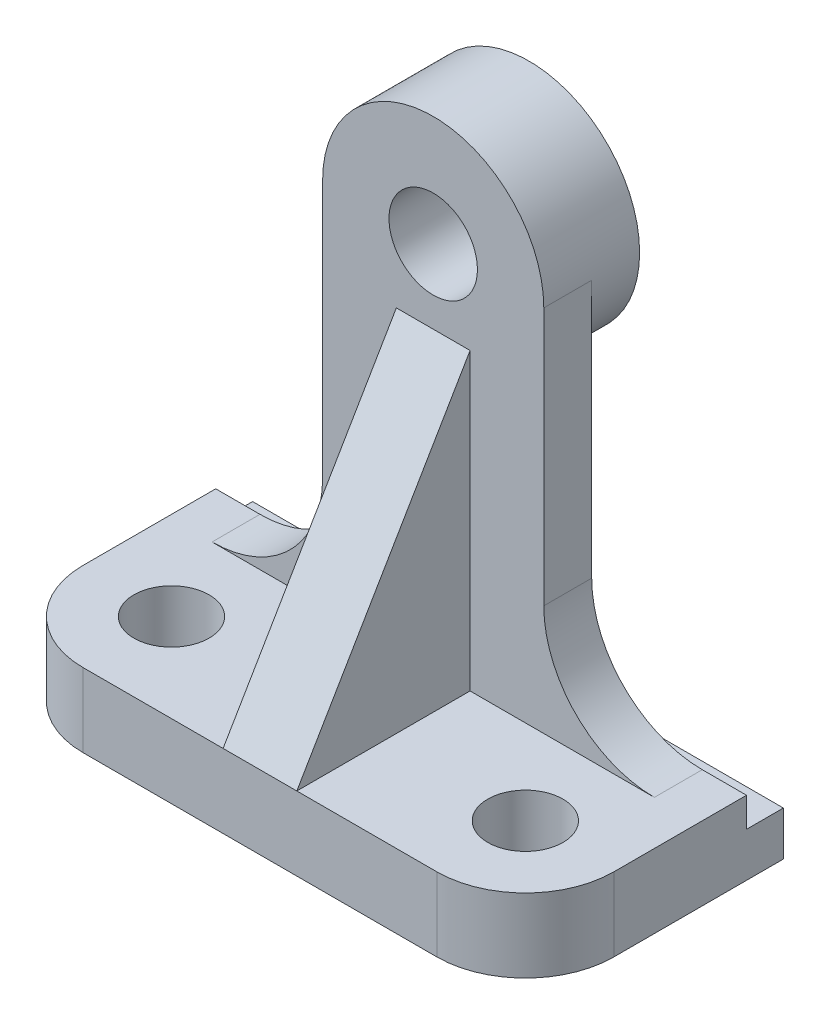
SolidWorks part; units mm, degrees
ref_plane "Front Plane" through (0, 0, 0) normal (0, 0, 1) x (1, 0, 0)
ref_plane "Top Plane" through (0, 0, 0) normal (0, 1, 0) x (1, 0, 0)
ref_plane "Right Plane" through (0, 0, 0) normal (1, 0, 0) x (0, 0, -1)
sketch "Sketch1" plane through (0, 0, 0) normal (0, 1, 0) x (1, 0, 0)
  line L0 (0, 22.4528) -> (0, -21.3843) construction
  line L1 (-36, -17.5) -> (36, -17.5)
  line L2 (-36, -17.5) -> (-36, 17.5)
  line L3 (-36, 17.5) -> (36, 17.5)
  line L4 (36, -17.5) -> (36, 17.5)
  line L5 (-36, -17.5) -> (36, 17.5) construction
  line L6 (-36, 17.5) -> (36, -17.5) construction
  circle A0 centre (24, -5.5) radius 5.1
  circle A1 centre (-24, -5.5) radius 5.1
  point P0 (0, 0)
  dimension "D4" = 10.2
  dimension "D1" = 35
  dimension "D2" = 72
  dimension "D3" = 24
  dimension "D5" = 12
extrude "Boss-Extrude1" add sketch "Sketch1" along normal blind 10
fillet "Fillet1" radius 12 2 edges at (-36, 5, 17.5) (36, 5, 17.5)
sketch "Sketch3" plane through (-36, 0, 0) normal (-1, 0, 0) x (0, 0, 1)
  line L0 (-17.5, 10) -> (-12.5, 10)
  line L1 (-17.5, 10) -> (5.5, 10) construction
  line L2 (-12.5, 10) -> (-12.5, 6)
  line L3 (-12.5, 6) -> (-17.5, 6)
  line L4 (-17.5, 10) -> (-17.5, 0) construction
  line L5 (-17.5, 10) -> (-17.5, 6)
  dimension "D1" = 5
  dimension "D2" = 4
extrude "Cut-Extrude1" cut sketch "Sketch3" against normal blind 75
sketch "Sketch6" plane through (0, 0, -12.5) normal (0, 0, -1) x (-1, 0, 0)
  line L0 (0, 0) -> (0, 75) construction
  line L1 (-15, 10) -> (15, 10)
  line L2 (-36, 10) -> (36, 10) construction
  line L3 (15, 10) -> (15, 60)
  line L4 (-15, 10) -> (-15, 60)
  circle A0 centre (0, 60) radius 15
  circle A1 centre (0, 60) radius 6
  point P8 (0, 10)
  line M8 (36, 10) -> (-36, 10)
  dimension "D2" = 30
  dimension "D3" = 12
  dimension "D1" = 75
extrude "Boss-Extrude2" add sketch "Sketch6" along normal mid plane 13 separate body contours L0 A0 A1 | A0 L0 A1 region at (7.0938, 60, -12.5) region at (-7.0938, 60, -12.5)
extrude "Boss-Extrude3" add sketch "Sketch6<3>" against normal blind 6.5 contours L1 L0 A0 L4 | L0 L3 A0 M8 region at (7.8495, 29.2562, -12.5) region at (-7.8495, 29.2562, -12.5)
sketch "Sketch6<3>" plane through (0, 0, -12.5) normal (0, 0, -1) x (-1, 0, 0) same geometry as "Sketch6"
fillet "Fillet2" radius 15 2 edges at (-15, 10, -9.25) (15, 10, -9.25)
sketch "Sketch7" plane through (0, 0, 0) normal (1, 0, 0) x (0, 0, -1)
  line L0 (-31.832, 0) -> (39.8785, 0) construction
  line L1 (6, 0) -> (6, 50) construction
  line L2 (6, 25) -> (6, 10) construction
  line L3 (-17.5, 0) -> (-17.5, 10) construction
  line L4 (-17.5, 10) -> (-17.5, 0) construction
  line L5 (-17.5, 10) -> (6, 10)
  line L6 (6, 10) -> (6, 50)
  line L7 (6, 50) -> (-17.5, 10)
  dimension "D1" = 50
  dimension "D2" = 10
extrude "Boss-Extrude4" add sketch "Sketch7" along normal mid plane 10
